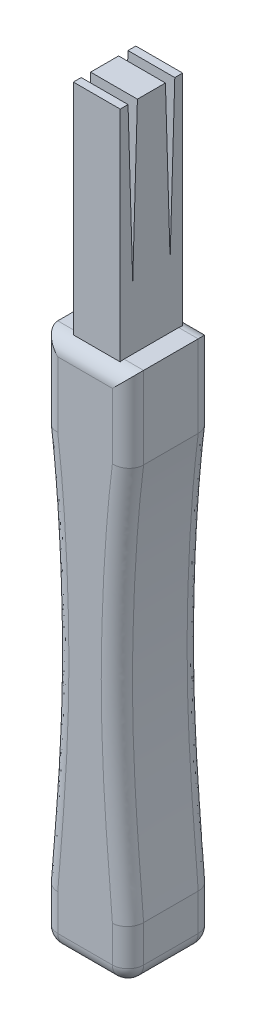
SolidWorks part; units mm, degrees
ref_plane "Front Plane" through (0, 0, 0) normal (0, 0, 1) x (1, 0, 0)
ref_plane "Top Plane" through (0, 0, 0) normal (0, 1, 0) x (1, 0, 0)
ref_plane "Right Plane" through (0, 0, 0) normal (1, 0, 0) x (0, 0, -1)
sketch "Sketch1" plane through (0, 0, 0) normal (0, 1, 0) x (1, 0, 0)
  line L1 (-17.4625, -17.4625) -> (17.4625, -17.4625)
  line L2 (-17.4625, -17.4625) -> (-17.4625, 17.4625)
  line L3 (-17.4625, 17.4625) -> (17.4625, 17.4625)
  line L4 (17.4625, -17.4625) -> (17.4625, 17.4625)
  line L5 (-17.4625, -17.4625) -> (17.4625, 17.4625) construction
  line L6 (-17.4625, 17.4625) -> (17.4625, -17.4625) construction
  point P0 (0, 0)
  dimension "D1" = 34.925
extrude "Boss-Extrude1" add sketch "Sketch1" along normal blind 304.8
sketch "Sketch2" plane through (0, 304.8, 0) normal (0, 1, 0) x (1, 0, 0)
  line L0 (0, 12.7) -> (0, 17.4625) construction
  line L1 (-9.525, 12.7) -> (9.525, 12.7)
  line L2 (-9.525, 12.7) -> (-9.525, -12.7)
  line L3 (-9.525, -12.7) -> (9.525, -12.7)
  line L4 (9.525, 12.7) -> (9.525, -12.7)
  line L5 (17.4625, 17.4625) -> (-17.4625, 17.4625) construction
  line L6 (0, -12.7) -> (0, -17.4625) construction
  line L7 (-17.4625, -17.4625) -> (17.4625, -17.4625) construction
  dimension "D1" = 19.05
  dimension "D2" = 25.4
extrude "Cut-Extrude1" cut sketch "Sketch2" against normal blind 88.9 flip side to cut
sketch "Sketch3" plane through (-9.525, 0, 0) normal (-1, 0, 0) x (0, 0, 1)
  line L0 (0, 304.8) -> (0, 215.9) construction
  line L1 (-12.7, 304.8) -> (12.7, 304.8) construction
  line L2 (-12.7, 215.9) -> (12.7, 215.9) construction
  line L3 (-9.5107, 304.8) -> (-7.6057, 241.3)
  line L4 (-7.6057, 241.3) -> (-5.7007, 304.8)
  line L5 (-5.7007, 304.8) -> (-9.5107, 304.8)
  line L6 (-7.6057, 304.8) -> (-7.6057, 241.3) construction
  line L7 (5.7007, 304.8) -> (9.5107, 304.8)
  line L8 (7.6057, 241.3) -> (5.7007, 304.8)
  line L9 (9.5107, 304.8) -> (7.6057, 241.3)
  dimension "D1" = 3.81
  dimension "D2" = 25.4
extrude "Cut-Extrude2" cut sketch "Sketch3" against normal through all
sketch "Sketch4" plane through (0, 0, -17.4625) normal (0, 0, 1) x (1, 0, 0)
  line L0 (0, 215.9) -> (0, 0) construction
  line L1 (-12.7, 215.9) -> (12.7, 215.9) construction
  line L2 (-17.4625, 215.9) -> (-17.4625, 0) construction
  line L4 (-17.4625, 182.5835) -> (-12.1724, 141.4152) construction
  line L5 (-12.1724, 141.4152) -> (-12.1724, 92.7257) construction
  line L6 (-12.1724, 92.7257) -> (-12.5459, 79.6713) construction
  line L7 (-12.5459, 79.6713) -> (-17.4625, 21.3069) construction
  line L8 (-17.4625, 182.5835) -> (-28.6612, 182.5835)
  line L9 (-28.6612, 182.5835) -> (-28.6612, 21.3069)
  line L10 (-28.6612, 21.3069) -> (-17.4625, 21.3069)
  line L11 (17.4625, 182.5835) -> (12.1724, 141.4152) construction
  line L12 (12.1724, 141.4152) -> (12.1724, 92.7257) construction
  line L13 (12.1724, 92.7257) -> (12.5459, 79.6713) construction
  line L14 (12.5459, 79.6713) -> (17.4625, 21.3069) construction
  line L15 (28.6612, 21.3069) -> (17.4625, 21.3069)
  line L16 (28.6612, 182.5835) -> (28.6612, 21.3069)
  line L17 (17.4625, 182.5835) -> (28.6612, 182.5835)
  spline S0 degree 4 poles (-17.4625, 182.5835) (-12.1724, 141.4152) (-12.1724, 92.7257) (-12.5459, 79.6713) (-17.4625, 21.3069) knots 0 0 0 0 0 1 1 1 1 1
  spline S1 degree 4 poles (17.4625, 182.5835) (12.1724, 141.4152) (12.1724, 92.7257) (12.5459, 79.6713) (17.4625, 21.3069) knots 0 0 0 0 0 1 1 1 1 1
extrude "Cut-Extrude3" cut sketch "Sketch4" along normal through all
fillet "Fillet1" radius 6.35 18 edges at (0, 0, -17.4625) (-17.4625, 0, 0) (0, 0, 17.4625) (17.4625, 0, 0) (17.4625, 199.2417, -17.4625) (0, 215.9, -17.4625) (-17.4625, 199.2417, -17.4625) (-17.4625, 10.6534, -17.4625) (17.4625, 10.6534, -17.4625) (17.4625, 10.6534, 17.4625) (-17.4625, 10.6534, 17.4625) (-17.4625, 199.2417, 17.4625) (0, 215.9, 17.4625) (17.4625, 199.2417, 17.4625)
